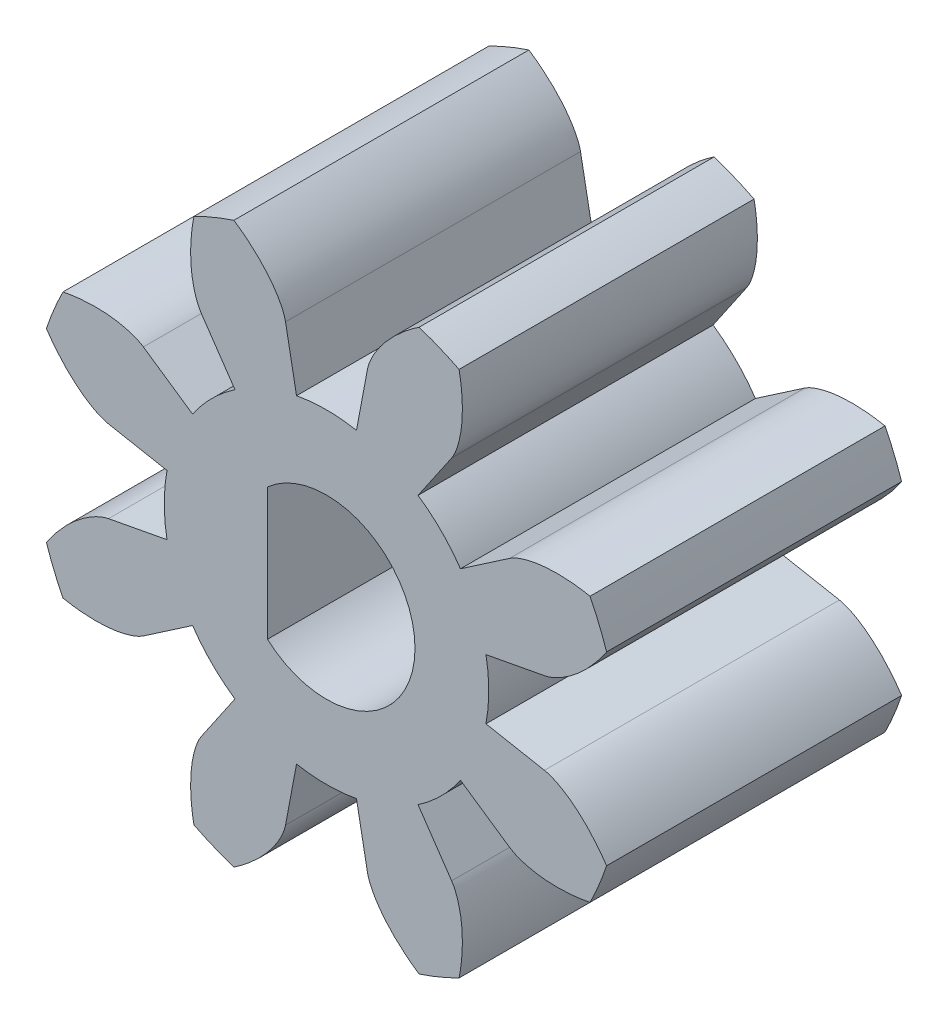
SolidWorks part; units mm, degrees
ref_plane "前视基准面" through (0, 0, 0) normal (0, 0, 1) x (1, 0, 0)
ref_plane "上视基准面" through (0, 0, 0) normal (0, 1, 0) x (1, 0, 0)
ref_plane "右视基准面" through (0, 0, 0) normal (1, 0, 0) x (0, 0, -1)
other "Configuration Table"
sketch "草图1" plane through (0, 0, 0) normal (0, 0, 1) x (1, 0, 0)
  line L0 (0, 0) -> (4, 0) construction
  line L1 (0, 0) -> (3.9231, 0.7804) construction
  line L2 (0, 0) -> (3.6941, 0.6945)
  line L3 (3.9231, 0.7804) -> (3.9231, -0.7804) construction
  line L4 (0, 0) -> (3.6941, -0.6945)
  circle A0 centre (0, 0) radius 5
  circle A1 centre (0, 0) radius 4 construction
  circle A2 centre (0, 0) radius 2.75
  circle A3 centre (0, 0) radius 3.7588 construction
  circle A4 centre (0, 0) radius 1.5
  spline S0 degree 4 poles (3.6941, 0.6945) (3.7222, 0.6998) (3.7997, 0.7204) (3.9403, 0.7826) (4.1522, 0.9137) (4.3976, 1.1246) (4.671, 1.4371) (4.933, 1.8476) (5.1531, 2.335) (5.3561, 3.0262) (5.443, 3.7431) (5.4253, 4.4924) (5.2827, 5.3729) (5.0281, 6.2292) (4.5902, 7.1708) (3.9479, 8.1289) (3.1749, 8.9843) (2.2938, 9.7273) (1.3255, 10.3516) (0.2887, 10.8537) (-0.7988, 11.2323) (-1.7817, 11.4556) (-2.5647, 11.5617) (-3.139, 11.6038) (-3.4958, 11.6181) (-3.788, 11.6215) (-4.0656, 11.6193) (-4.3699, 11.6068) (-4.6041, 11.5939) (-4.8725, 11.5704) (-5.1429, 11.5429) (-5.4129, 11.5084) (-5.885, 11.4372) (-6.2665, 11.3559) (-6.6616, 11.2688) (-6.8509, 11.2136) (-6.9779, 11.1808) knots 0 0 0 0 0 0.005604 0.015718 0.02996 0.048734 0.068727 0.096889 0.125051 0.153212 0.209535 0.237696 0.271429 0.327752 0.384075 0.440398 0.496721 0.553044 0.609367 0.66569 0.722013 0.778336 0.806497 0.820578 0.834659 0.84874 0.86282 0.876901 0.890982 0.900036 0.909091 0.931818 0.954545 0.977273 1 1 1 1 1 construction
  spline S1 degree 4 poles (3.6941, 0.6945) (3.7222, 0.6998) (3.7997, 0.7204) (3.9403, 0.7826) (4.1522, 0.9137) (4.3976, 1.1246) (4.671, 1.4371) (4.933, 1.8476) (5.1531, 2.335) (5.3561, 3.0262) (5.443, 3.7431) (5.4253, 4.4924) (5.2827, 5.3729) (5.0281, 6.2292) (4.5902, 7.1708) (3.9479, 8.1289) (3.1749, 8.9843) (2.2938, 9.7273) (1.3255, 10.3516) (0.2887, 10.8537) (-0.7988, 11.2323) (-1.7817, 11.4556) (-2.5647, 11.5617) (-3.139, 11.6038) (-3.4958, 11.6181) (-3.788, 11.6215) (-4.0656, 11.6193) (-4.3699, 11.6068) (-4.6041, 11.5939) (-4.8725, 11.5704) (-5.031, 11.5543) (-5.1147, 11.5449) (-5.1564, 11.5399) knots 0 0 0 0 0 0.005604 0.015718 0.02996 0.048734 0.068727 0.096889 0.125051 0.153212 0.209535 0.237696 0.271429 0.327752 0.384075 0.440398 0.496721 0.553044 0.609367 0.66569 0.722013 0.778336 0.806497 0.820578 0.834659 0.84874 0.86282 0.876901 0.890982 0.900036 0.909091 0.909091 0.909091 0.909091 0.909091
  spline S2 degree 4 poles (3.6941, -0.6945) (3.7222, -0.6998) (3.7997, -0.7204) (3.9403, -0.7826) (4.1522, -0.9137) (4.3976, -1.1246) (4.671, -1.4371) (4.933, -1.8476) (5.1531, -2.335) (5.3561, -3.0262) (5.443, -3.7431) (5.4253, -4.4924) (5.2827, -5.3729) (5.0281, -6.2292) (4.5902, -7.1708) (3.9479, -8.1289) (3.1749, -8.9843) (2.2938, -9.7273) (1.3255, -10.3516) (0.2887, -10.8537) (-0.7988, -11.2323) (-1.7817, -11.4556) (-2.5647, -11.5617) (-3.139, -11.6038) (-3.4958, -11.6181) (-3.788, -11.6215) (-4.0656, -11.6193) (-4.3699, -11.6068) (-4.6041, -11.5939) (-4.8725, -11.5704) (-5.1429, -11.5429) (-5.4129, -11.5084) (-5.885, -11.4372) (-6.2665, -11.3559) (-6.6616, -11.2688) (-6.8509, -11.2136) (-6.9779, -11.1808) knots 0 0 0 0 0 0.005604 0.015718 0.02996 0.048734 0.068727 0.096889 0.125051 0.153212 0.209535 0.237696 0.271429 0.327752 0.384075 0.440398 0.496721 0.553044 0.609367 0.66569 0.722013 0.778336 0.806497 0.820578 0.834659 0.84874 0.86282 0.876901 0.890982 0.900036 0.909091 0.931818 0.954545 0.977273 1 1 1 1 1 construction
  spline S3 degree 4 poles (3.6941, -0.6945) (3.7222, -0.6998) (3.7997, -0.7204) (3.9403, -0.7826) (4.1522, -0.9137) (4.3976, -1.1246) (4.671, -1.4371) (4.933, -1.8476) (5.1531, -2.335) (5.3561, -3.0262) (5.443, -3.7431) (5.4253, -4.4924) (5.2827, -5.3729) (5.0281, -6.2292) (4.5902, -7.1708) (3.9479, -8.1289) (3.1749, -8.9843) (2.2938, -9.7273) (1.3255, -10.3516) (0.2887, -10.8537) (-0.7988, -11.2323) (-1.7817, -11.4556) (-2.5647, -11.5617) (-3.139, -11.6038) (-3.4958, -11.6181) (-3.788, -11.6215) (-4.0656, -11.6193) (-4.3699, -11.6068) (-4.6041, -11.5939) (-4.8725, -11.5704) (-5.031, -11.5543) (-5.1147, -11.5449) (-5.1564, -11.5399) knots 0 0 0 0 0 0.005604 0.015718 0.02996 0.048734 0.068727 0.096889 0.125051 0.153212 0.209535 0.237696 0.271429 0.327752 0.384075 0.440398 0.496721 0.553044 0.609367 0.66569 0.722013 0.778336 0.806497 0.820578 0.834659 0.84874 0.86282 0.876901 0.890982 0.900036 0.909091 0.909091 0.909091 0.909091 0.909091
  point P15 (3.9231, 0)
  dimension "齿顶圆直径" = 10
  dimension "分度圆直径" = 8
  dimension "齿根圆直径" = 5.5
  dimension "基圆直径" = 7.5175
  dimension "内孔直径" = 3
  dimension "渐近线镜像线夹角" = 11.25
extrude "凸台-拉伸1" add sketch "草图1" along normal blind 5 contours A0 | A4
extrude "切除-拉伸1" cut sketch "草图1<3>" along normal through all contours A2 S3 A0 S1 region at (4.0533, 0, 0)
sketch "草图1<3>" plane through (0, 0, 0) normal (0, 0, 1) x (1, 0, 0) same geometry as "草图1"
pattern_circular "阵列(圆周)1" count 8 every 45 about axis through (0, 0, 5) along (0, 0, 1) of "切除-拉伸1"
sketch "草图2" plane through (0, 0, 5) normal (0, 0, 1) x (1, 0, 0)
  line L0 (-1, 1.1843) -> (-1, -1.1843)
  circle A0 centre (0, 0) radius 1.55
  circle M39 centre (0, 0) radius 1.5
  dimension "D1" = 3.1
  dimension "D2" = 1
extrude "凸台-拉伸2" add sketch "草图2" against normal through all contours A0
extrude "切除-拉伸2" cut sketch "草图2<3>" against normal through all contours L0 M39 region at (0.148, 0, 5)
sketch "草图2<3>" plane through (0, 0, 5) normal (0, 0, 1) x (1, 0, 0) same geometry as "草图2"
equation "\"m\"= 1'模数"
equation "\"z\"= 8'齿数"
equation "\"a\"= 20度'压力角"
equation "\"d\"= \"m\" * \"z\"'分度圆直径"
equation "\"da\"= ( \"z\" + 2 ) * \"m\"'齿顶圆直径"
equation "\"df\"= ( \"z\" - 2.5 ) * \"m\"'齿根圆直径"
equation "\"s\"= 0.5 * PI * \"m\"'分度圆齿厚"
equation "\"r\"= 0.38 * \"m\"'齿根圆角"
equation "\"B\"= 0.3 * \"d\"'齿厚"
equation "\"db\"= \"m\" * \"z\" * cos ( \"a\" )'基圆直径"
equation "\"rb\"= \"db\" / 2'基圆半径"
equation "\"齿顶圆直径@草图1\"= \"da\""
equation "\"分度圆直径@草图1\"= \"d\""
equation "\"齿根圆直径@草图1\"= \"df\""
equation "\"基圆直径@草图1\"= \"db\""
equation "\"渐近线镜像线夹角@草图1\"= 360 / 4 / \"z\""
equation "\"h\"= 5'齿轮厚度"
equation "\"ir\"= 3'内孔直径"
equation "\"内孔直径@草图1\"= \"ir\""
equation "\"齿轮厚@凸台-拉伸1\"= \"h\""
equation "\"齿轮夹角@阵列(圆周)1\"= 360 / \"z\""
equation "\"齿数@阵列(圆周)1\"= \"z\""
